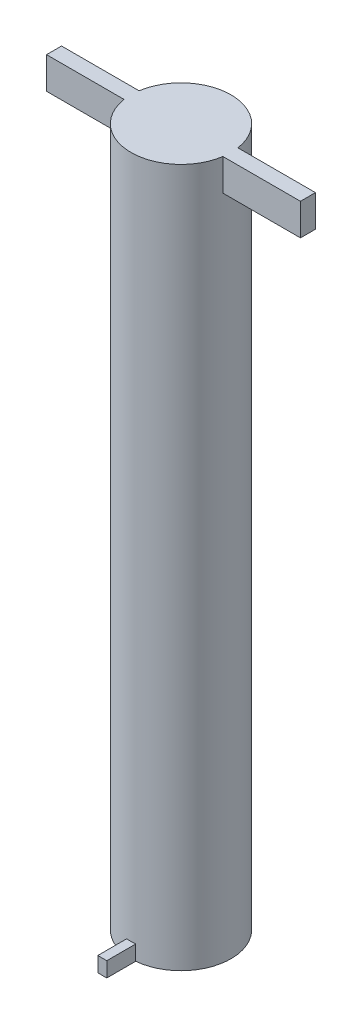
SolidWorks part; units mm, degrees
ref_plane "Front Plane" through (0, 0, 0) normal (0, 0, 1) x (1, 0, 0)
ref_plane "Top Plane" through (0, 0, 0) normal (0, 1, 0) x (1, 0, 0)
ref_plane "Right Plane" through (0, 0, 0) normal (1, 0, 0) x (0, 0, -1)
sketch "Sketch1" plane through (0, 0, 0) normal (0, 1, 0) x (1, 0, 0)
  circle A0 centre (0, 0) radius 10
  dimension "D1" = 20
extrude "Boss-Extrude1" add sketch "Sketch1" along normal blind 139.7
sketch "Sketch3" plane through (0, 0, 0) normal (0, -1, 0) x (1, 0, 0)
  line L1 (-0.9, 15.75) -> (0.9, 15.75)
  line L2 (-0.9, 15.75) -> (-0.9, 9.3548)
  line L4 (0.9, 15.75) -> (0.9, 9.3548)
  arc A0 (0.9, 9.3548) -> (-0.9, 9.3548) centre (0, 0) ccw
  dimension "D1" = 0.9
  dimension "D3" = 15.75
extrude "Boss-Extrude2" add sketch "Sketch3" against normal blind 3
sketch "Sketch4" plane through (0, 139.7, 0) normal (0, 1, 0) x (1, 0, 0)
  line L1 (-25.4, 1.5) -> (25.4, 1.5)
  line L2 (-25.4, 1.5) -> (-25.4, -1.5)
  line L3 (-25.4, -1.5) -> (25.4, -1.5)
  line L4 (25.4, 1.5) -> (25.4, -1.5)
  point P4 (-25.4, 0)
  point P5 (0, 1.5)
  dimension "D1" = 50.8
  dimension "D2" = 3
extrude "Boss-Extrude3" add sketch "Sketch4" against normal blind 6.35
sketch "Sketch5" plane through (0, 0, 0) normal (0, -1, 0) x (1, 0, 0)
  circle A0 centre (0, 0) radius 6.25
  dimension "D1" = 12.5
extrude "Cut-Extrude1" cut sketch "Sketch5" against normal blind 4
